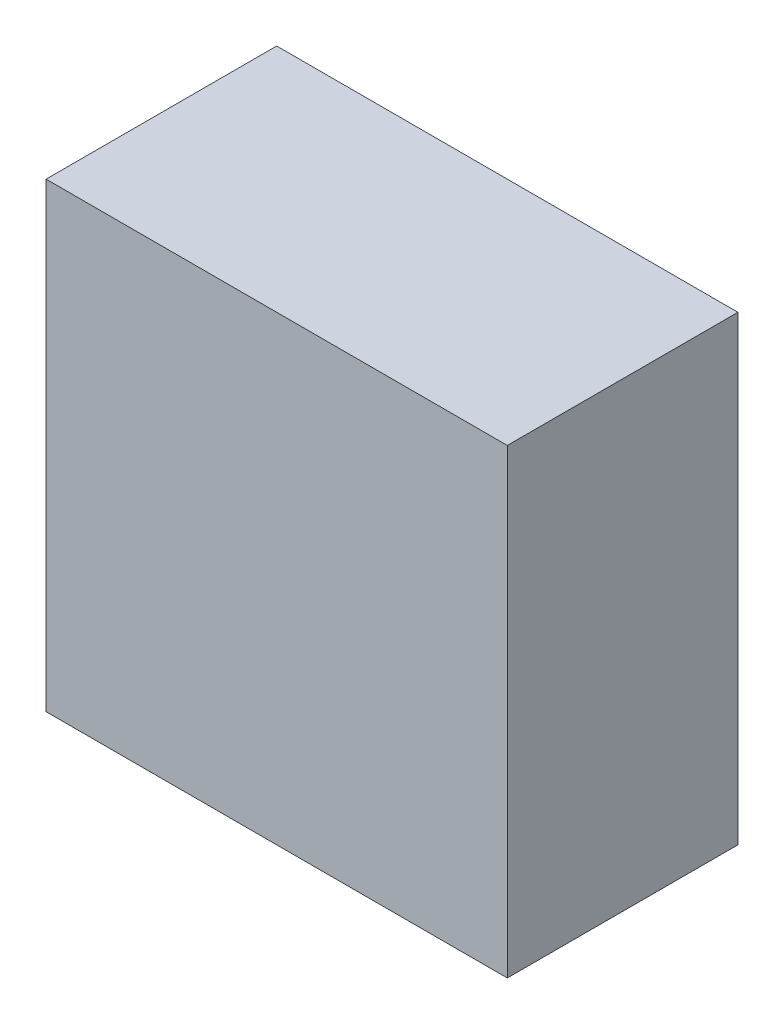
SolidWorks part; units mm, degrees
ref_plane "Front Plane" through (0, 0, 0) normal (0, 0, 1) x (1, 0, 0)
ref_plane "Top Plane" through (0, 0, 0) normal (0, 1, 0) x (1, 0, 0)
ref_plane "Right Plane" through (0, 0, 0) normal (1, 0, 0) x (0, 0, -1)
sketch "Sketch1" plane through (0, 0, 0) normal (0, 0, 1) x (1, 0, 0)
  line L1 (0, 0) -> (40, 0)
  line L2 (0, 0) -> (0, 40)
  line L3 (0, 40) -> (40, 40)
  line L4 (40, 0) -> (40, 40)
extrude "Boss-Extrude1" add sketch "Sketch1" along normal blind 10 and the other way blind 10
sketch "Sketch2" plane through (0, 0, 0) normal (0, 0, 1) x (1, 0, 0)
  line L1 (0, 0) -> (10, 0)
  line L2 (0, 0) -> (0, 10)
  line L3 (0, 10) -> (10, 10)
  line L4 (10, 0) -> (10, 10)
extrude "Cut-Extrude1" cut sketch "Sketch2" along normal blind 5
